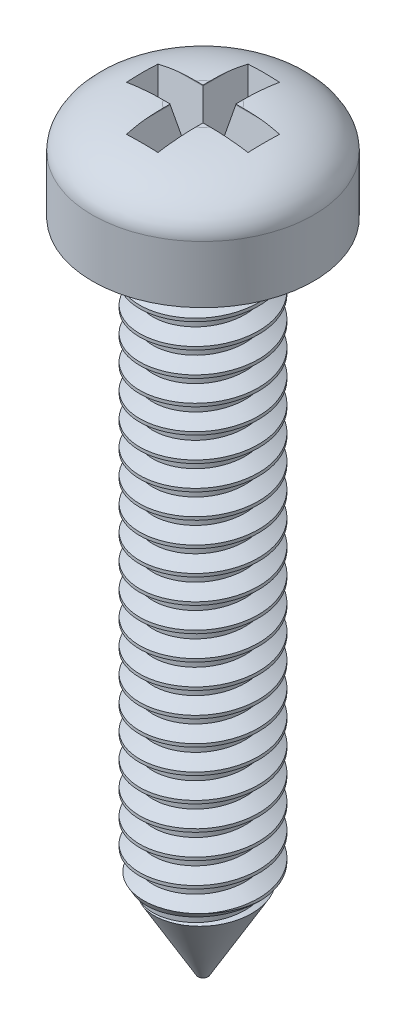
SolidWorks part; units mm, degrees
material "AISI 304"
ref_plane "Plano frontal" through (0, 0, 0) normal (0, 0, 1) x (1, 0, 0)
ref_plane "Plano superior" through (0, 0, 0) normal (0, 1, 0) x (1, 0, 0)
ref_plane "Plano direito" through (0, 0, 0) normal (1, 0, 0) x (0, 0, -1)
sketch "Esboço1" plane through (0, 0, 0) normal (0, 1, 0) x (1, 0, 0)
  circle A0 centre (0, 0) radius 2.7
  dimension "D1" = 5.4
extrude "Ressalto-extrusão1" add sketch "Esboço1" along normal blind 2.4 contours A0
fillet "Filete8" radius 1 1 edges at (0, 2.4, 2.7) second distance 2 first distance on face at (0, 2.4, 2.7)
sketch "Esboço3" plane through (0, 2.4, 0) normal (0, 1, 0) x (1, 0, 0)
  line L0 (0.4, 0.4) -> (0.4, 1.5)
  line L7 (-0.4, -1.5) -> (0.4, -1.5)
  line L8 (-0.4, -1.5) -> (-0.4, -0.4)
  line L9 (-0.4, 1.5) -> (0.4, 1.5)
  line L10 (0.4, -1.5) -> (0.4, -0.4)
  line L11 (-0.4, -1.5) -> (0.4, 1.5) construction
  line L12 (-0.4, 1.5) -> (0.4, -1.5) construction
  line L13 (-1.5, -0.4) -> (-0.4, -0.4)
  line L14 (-1.5, -0.4) -> (-1.5, 0.4)
  line L15 (-1.5, 0.4) -> (-0.4, 0.4)
  line L16 (1.5, -0.4) -> (1.5, 0.4)
  line L17 (-1.5, -0.4) -> (1.5, 0.4) construction
  line L18 (-1.5, 0.4) -> (1.5, -0.4) construction
  line L19 (0.4, 0.4) -> (1.5, 0.4)
  line L21 (-0.4, 0.4) -> (-0.4, 1.5)
  line L24 (0.4, -0.4) -> (1.5, -0.4)
  point P0 (0, 0)
  point P5 (0, 0)
  dimension "D1" = 0.8
  dimension "D2" = 0.8
  dimension "D3" = 3
  dimension "D4" = 3
extrude "Corte-extrusão1" cut sketch "Esboço3" against normal blind 1.5
chamfer "Chanfro3" distance 1.48 angle 12 12 edges at (0.4, 0.9, -0.95) (0.95, 0.9, -0.4) (1.5, 0.9, 0) (0.95, 0.9, 0.4) (0.4, 0.9, 0.95) (0, 0.9, 1.5) (-0.4, 0.9, 0.95) (-0.95, 0.9, 0.4) (-1.5, 0.9, 0) (-0.95, 0.9, -0.4) (-0.4, 0.9, -0.95) (0, 0.9, -1.5) first distance on face at (0.4, 1.7905, -0.7649) first distance on face at (0.9849, 1.7714, -0.4) first distance on face at (1.5, 1.6053, 0.0002) first distance on face at (0.7649, 1.7905, 0.4) first distance on face at (0.4, 1.7714, 0.9849) first distance on face at (-0.0002, 1.6053, 1.5) first distance on face at (-0.4, 1.7905, 0.7649) first distance on face at (-0.9849, 1.7714, 0.4) first distance on face at (-1.5, 1.6053, -0.0002) first distance on face at (-0.7649, 1.7905, -0.4) first distance on face at (-0.4, 1.7714, -0.9849) first distance on face at (0.0002, 1.6053, -1.5)
sketch "Esboço4" plane through (0, 0, 0) normal (0, -1, 0) x (1, 0, 0)
  circle A0 centre (0, 0) radius 1.45
  dimension "D1" = 2.9
extrude "Ressalto-extrusão2" add sketch "Esboço4" along normal blind 16
chamfer "Chanfro4" distance 2.3 angle 30 1 edges at (0, -16, -1.45) first distance on face at (0, -16, -1.45)
fillet "Filete2" radius 0.2 1 edges at (0, 0, -1.45)
thread "Rosca1" pitch 0.6 method cut profile "Perfil da rosca1" start angle 0, offset 0, length 0, pitch 0.6, diameter 2.9
ref_plane "Plano1" through (-1.45, -0.2, 0) normal (0, 0, 1) x (-1, 0, 0)
sketch "Perfil da rosca1" plane through (-1.45, -0.2, 0) normal (0, 0, 1) x (-1, 0, 0)
  line L0 (0, 0) -> (0, 0.6) construction
  line L11 (0, 0) -> (0, 0.525)
  line L12 (0, 0.525) -> (-0.3248, 0.3375)
  line L13 (-0.3248, 0.3375) -> (-0.3248, 0.1875)
  line L15 (-0.3248, 0.1875) -> (0, 0)
  line L17 (-0.3248, 0.2625) -> (0, 0.2625) construction
  point P2 (0, 0)
  dimension "Pitch" = 0.6
  dimension "Profile_Angle" = 60
  dimension "Profile_Land" = 0.15
  dimension "Profile_Height" = 0.3248
